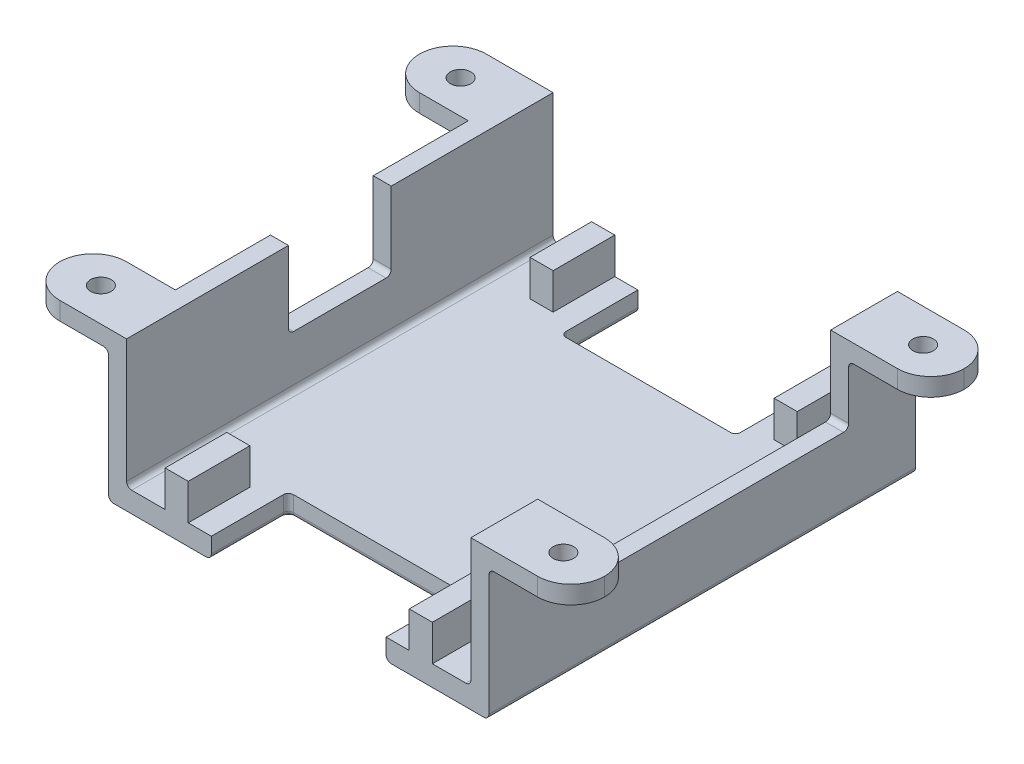
SolidWorks part; units mm, degrees
material "ABS"
ref_plane "Front Plane" through (0, 0, 0) normal (0, 0, 1) x (1, 0, 0)
ref_plane "Top Plane" through (0, 0, 0) normal (0, 1, 0) x (1, 0, 0)
ref_plane "Right Plane" through (0, 0, 0) normal (1, 0, 0) x (0, 0, -1)
sketch "Sketch1" plane through (0, 0, 0) normal (0, 1, 0) x (1, 0, 0)
  line L1 (-37, 26.5) -> (37, 26.5)
  line L2 (-37, 26.5) -> (-37, -26.5)
  line L3 (-37, -26.5) -> (37, -26.5)
  line L4 (37, 26.5) -> (37, -26.5)
  line L5 (-37, 26.5) -> (37, -26.5) construction
  line L6 (-37, -26.5) -> (37, 26.5) construction
  point P0 (0, 0)
  dimension "D1" = 74
  dimension "D2" = 53
extrude "Boss-Extrude1" add sketch "Sketch1" along normal blind 4
sketch "Sketch2" plane through (0, 4, 0) normal (0, 1, 0) x (1, 0, 0)
  line L0 (-37, -26.5) -> (37, -26.5) construction
  line L1 (-37, 26.5) -> (-33.5, 26.5)
  line L2 (-37, 26.5) -> (-37, -26.5)
  line L3 (-37, -26.5) -> (-33.5, -26.5)
  line L4 (-33.5, 26.5) -> (-33.5, -26.5)
  dimension "D1" = 3.5
extrude "Boss-Extrude2" add sketch "Sketch2" along normal blind 25
mirror "Mirror1" about plane through (0, 0, 0) normal (1, 0, 0) of "Boss-Extrude2"
sketch "Sketch3" plane through (-37, 0, 0) normal (-1, 0, 0) x (0, 0, 1)
  line L0 (-26.5, 29) -> (26.5, 29) construction
  line L1 (-10, 29) -> (10, 29)
  line L2 (-10, 29) -> (-10, 14)
  line L3 (-10, 14) -> (10, 14)
  line L4 (10, 29) -> (10, 14)
  line L5 (-26.5, 29) -> (-26.5, 0) construction
  dimension "D1" = 15
  dimension "D2" = 20
  dimension "D3" = 16.5
extrude "Cut-Extrude1" cut sketch "Sketch3" against normal up to next
sketch "Sketch5" plane through (0, 0, -26.5) normal (0, 0, -1) x (-1, 0, 0)
  line L0 (-33.5, 4) -> (33.5, 4) construction
  line L1 (37, 0) -> (17, 0)
  line L2 (37, 0) -> (37, 4)
  line L3 (37, 4) -> (17, 4)
  line L4 (17, 0) -> (17, 4)
  dimension "D1" = 20
extrude "Boss-Extrude4" add sketch "Sketch5" along normal blind 15
mirror "Mirror3" about plane through (0, 0, 0) normal (0, 0, 1) of "Boss-Extrude4"
mirror "Mirror4" about plane through (0, 0, 0) normal (1, 0, 0) of "Mirror3"
sketch "Sketch6" plane through (0, 4, 0) normal (0, 1, 0) x (1, 0, 0)
  line L1 (-37, 41.5) -> (-33.5, 41.5)
  line L2 (-37, 41.5) -> (-37, 26.5)
  line L3 (-37, 26.5) -> (-33.5, 26.5)
  line L4 (-33.5, 41.5) -> (-33.5, 26.5)
extrude "Boss-Extrude5" add sketch "Sketch6" along normal up to surface (25 mm away) up to face at (-35.25, 29, -18.25)
mirror "Mirror5" about plane through (0, 0, 0) normal (0, 0, 1) of "Boss-Extrude5"
mirror "Mirror6" about plane through (0, 0, 0) normal (1, 0, 0) of "Mirror5"
sketch "Sketch7" plane through (0, 4, 0) normal (0, 1, 0) x (1, 0, 0)
  line L0 (-33.5, 41.5) -> (-17, 41.5) construction
  line L1 (-26, 41.5) -> (-21.5, 41.5)
  line L2 (-26, 41.5) -> (-26, 29.5)
  line L3 (-26, 29.5) -> (-21.5, 29.5)
  line L4 (-21.5, 41.5) -> (-21.5, 29.5)
  line L5 (17, 26.5) -> (-17, 26.5) construction
  dimension "D1" = 4.5
  dimension "D2" = 7.5
  dimension "D3" = 3
extrude "Boss-Extrude6" add sketch "Sketch7" along normal blind 7
mirror "Mirror7" about plane through (0, 0, 0) normal (0, 0, 1) of "Boss-Extrude6"
mirror "Mirror8" about plane through (0, 0, 0) normal (1, 0, 0) of "Mirror7"
sketch "Sketch8" plane through (-37, 0, 0) normal (-1, 0, 0) x (0, 0, 1)
  line L1 (-41.5, 29) -> (-28.5, 29)
  line L2 (-41.5, 29) -> (-41.5, 25.5)
  line L3 (-41.5, 25.5) -> (-28.5, 25.5)
  line L4 (-28.5, 29) -> (-28.5, 25.5)
  dimension "D1" = 3.5
  dimension "D2" = 13
extrude "Boss-Extrude7" add sketch "Sketch8" along normal blind 16
mirror "Mirror9" about plane through (0, 0, 0) normal (0, 0, 1) of "Boss-Extrude7"
mirror "Mirror10" about plane through (0, 0, 0) normal (1, 0, 0) of "Mirror9"
sketch "Sketch9" plane through (37, 0, 0) normal (1, 0, 0) x (0, 0, -1)
  line L0 (28.5, 14) -> (-28.5, 29) construction
  line L5 (-28.5, 14) -> (28.5, 29) construction
  line L11 (28.5, 14) -> (-28.5, 14)
  line L12 (28.5, 14) -> (28.5, 29)
  line L13 (28.5, 29) -> (-28.5, 29)
  line L14 (-28.5, 14) -> (-28.5, 29)
  line L15 (28.5, 14) -> (-28.5, 29) construction
  line L16 (28.5, 29) -> (-28.5, 14) construction
  point P5 (0, 21.5)
  dimension "D1" = 57
  dimension "D2" = 15
extrude "Cut-Extrude2" cut sketch "Sketch9" against normal up to next
sketch "Sketch11" plane through (0, 25.5, 0) normal (0, -1, 0) x (1, 0, 0)
  line L0 (-53, 35) -> (-37, 35) construction
  line L1 (-53, 41.5) -> (-53, 28.5) construction
  line L2 (-37, 41.5) -> (-37, 28.5) construction
  line L3 (-53, -35) -> (-37, -35) construction
  line L4 (-53, -41.5) -> (-53, -28.5) construction
  line L5 (-37, -41.5) -> (-37, -28.5) construction
  line L6 (37, 35) -> (53, 35) construction
  line L7 (37, 41.5) -> (37, 28.5) construction
  line L8 (53, 41.5) -> (53, 28.5) construction
  line L9 (53, -35) -> (37, -35) construction
  line L10 (53, -41.5) -> (53, -28.5) construction
  line L11 (37, 41.5) -> (37, -41.5) construction
  point P24 (45, -35)
  point P25 (45, 35)
  point P26 (-45, 35)
  point P27 (-45, -35)
hole_wizard "Ø4.0mm Clearance Dowel Hole1" positions "Sketch13" profile "Sketch14" hole size "Ø4.0" standard "ANSI Metric" end condition through all
sketch "Sketch13" plane through (0, 25.5, 0) normal (0, -1, 0) x (-1, 0, 0)
  point P0 (-45, 35)
  point P3 (-45, -35)
  point P6 (45, 35)
  point P9 (45, -35)
sketch "Sketch14" plane through (45, 25.5, -35) normal (1, 0, 0) x (0, 0, -1)
  line L0 (0, 0) -> (0, 3.5)
  line L1 (0, 3.5) -> (2, 3.5)
  line L2 (2, 3.5) -> (2, 0)
  line L5 (2, 0) -> (0, 0)
  line L11 (0, -6.35) -> (0, 107.95) construction
  dimension "Thru Hole Dia." = 4
  dimension "Thru Hole Depth" = 3.5
sketch "Sketch15" plane through (0, 0, 28.5) normal (0, 0, -1) x (-1, 0, 0)
  line L1 (53, 29) -> (37, 29)
  line L2 (53, 29) -> (53, 25.5)
  line L3 (53, 25.5) -> (37, 25.5)
  line L4 (37, 29) -> (37, 25.5)
fillet "Fillet1" radius 6.5 8 edges at (53, 27.25, -28.5) (53, 27.25, -41.5) (53, 27.25, 28.5) (53, 27.25, 41.5) (-53, 27.25, -41.5) (-53, 27.25, -28.5) (-53, 27.25, 28.5) (-53, 27.25, 41.5)
fillet "Fillet2" radius 1 14 edges at (-33.5, 4, 0) (17, 2, -26.5) (-17, 2, -26.5) (-17, 2, 26.5) (17, 2, 26.5) (-37, 25.5, -35) (-37, 25.5, 35) (-35.25, 14, -10) (-35.25, 14, 10) (35.25, 14, 28.5) (35.25, 14, -28.5) (33.5, 4, 0) (37, 25.5, -35) (37, 25.5, 35)
fillet "Fillet3" radius 1 12 edges at (-17, 0, -34.5) (-16.7071, 0, -26.7929) (0, 0, -26.5) (16.7071, 0, -26.7929) (-17, 0, 34.5) (-16.7071, 0, 26.7929) (0, 0, 26.5) (16.7071, 0, 26.7929) (17, 0, -34.5) (17, 0, 34.5) (-37, 0, 0) (37, 0, 0)
